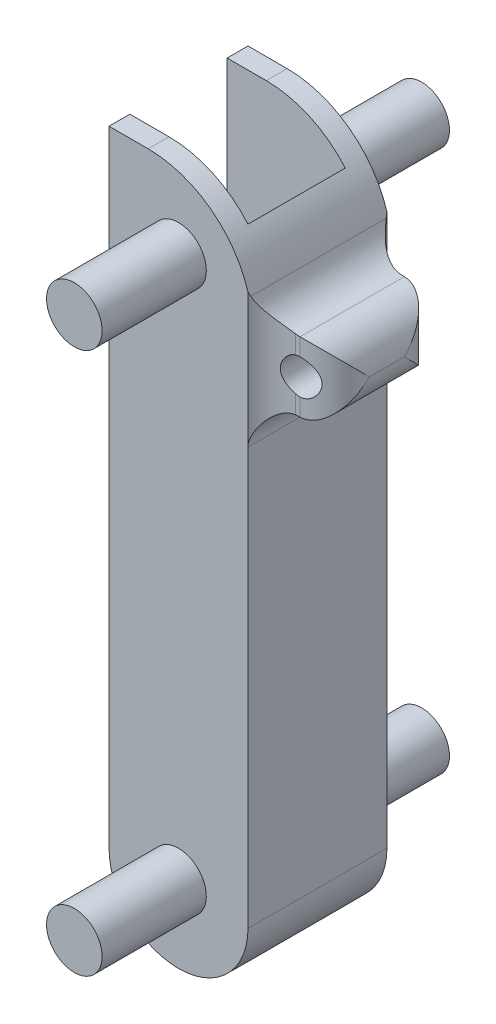
SolidWorks part; units mm, degrees
ref_plane "Front Plane" through (0, 0, 0) normal (0, 0, 1) x (1, 0, 0)
ref_plane "Top Plane" through (0, 0, 0) normal (0, 1, 0) x (1, 0, 0)
ref_plane "Right Plane" through (0, 0, 0) normal (1, 0, 0) x (0, 0, -1)
sketch "Sketch1" plane through (0, 0, 0) normal (1, 0, 0) x (0, 0, -1)
  line L1 (-10, 0) -> (10, 0)
  line L2 (-10, 0) -> (-10, 100)
  line L3 (-10, 100) -> (10, 100)
  line L4 (10, 0) -> (10, 100)
  point P4 (0, 0)
  dimension "D1" = 20
  dimension "D2" = 100
extrude "Boss-Extrude1" add sketch "Sketch1" along normal mid plane 20
sketch "Sketch3" plane through (0, 0, 0) normal (0, 0, 1) x (1, 0, 0)
  line L0 (10, 0) -> (-10, 0) construction
  line L1 (10, 100) -> (-10, 100) construction
  circle A0 centre (0, 11) radius 4
  circle A1 centre (0, 89) radius 4
  dimension "D1" = 8
  dimension "D3" = 11
  dimension "D2" = 11
extrude "Boss-Extrude2" add sketch "Sketch3" along normal mid plane 50
fillet "Fillet1" radius 10 2 edges at (10, 0, 0) (-10, 0, 0)
sketch "Sketch5" plane through (0, 0, 0) normal (0, 0, 1) x (1, 0, 0)
  line L0 (10, 85) -> (20, 85)
  line L1 (10, 100) -> (10, 10) construction
  line L2 (20, 85) -> (20, 75)
  line L3 (20, 75) -> (10, 75)
  line L4 (10, 100) -> (-10, 100) construction
  line L5 (10, 85) -> (10, 75)
  circle A0 centre (15, 80) radius 2.5
  point P11 (15, 85)
  point P13 (20, 80)
  dimension "D4" = 5
  dimension "D1" = 10
  dimension "D2" = 10
  dimension "D3" = 15
extrude "Boss-Extrude3" add sketch "Sketch5" along normal mid plane 15
fillet "Fillet2" radius 5 8 edges at (20, 80, -7.5) (20, 80, 7.5) (10, 80, 7.5) (10, 80, -7.5) (10, 85, 0) (20, 85, 0) (20, 75, 0) (10, 75, 0)
sketch "Sketch6" plane through (0, 100, 0) normal (0, 1, 0) x (1, 0, 0)
  line L0 (-10, 7) -> (7, 7)
  line L1 (-10, 10) -> (-10, -10) construction
  line L2 (7, 7) -> (7, -7)
  line L3 (7, -7) -> (-10, -7)
  line L4 (10, 10) -> (-10, 10) construction
  line L6 (10, -10) -> (-10, -10) construction
  line L7 (-10, 7) -> (-10, -7)
  line L8 (10, -10) -> (10, 10) construction
  dimension "D1" = 3
  dimension "D3" = 3
  dimension "D2" = 3
extrude "Cut-Extrude1" cut sketch "Sketch6" against normal through all both and the other way through all
fillet "Fillet3" radius 15 1 edges at (10, 100, 0)
equation "\"D3@Sketch6\"=\"D1@Sketch6\""
equation "\"D2@Sketch6\"=\"D1@Sketch6\""
